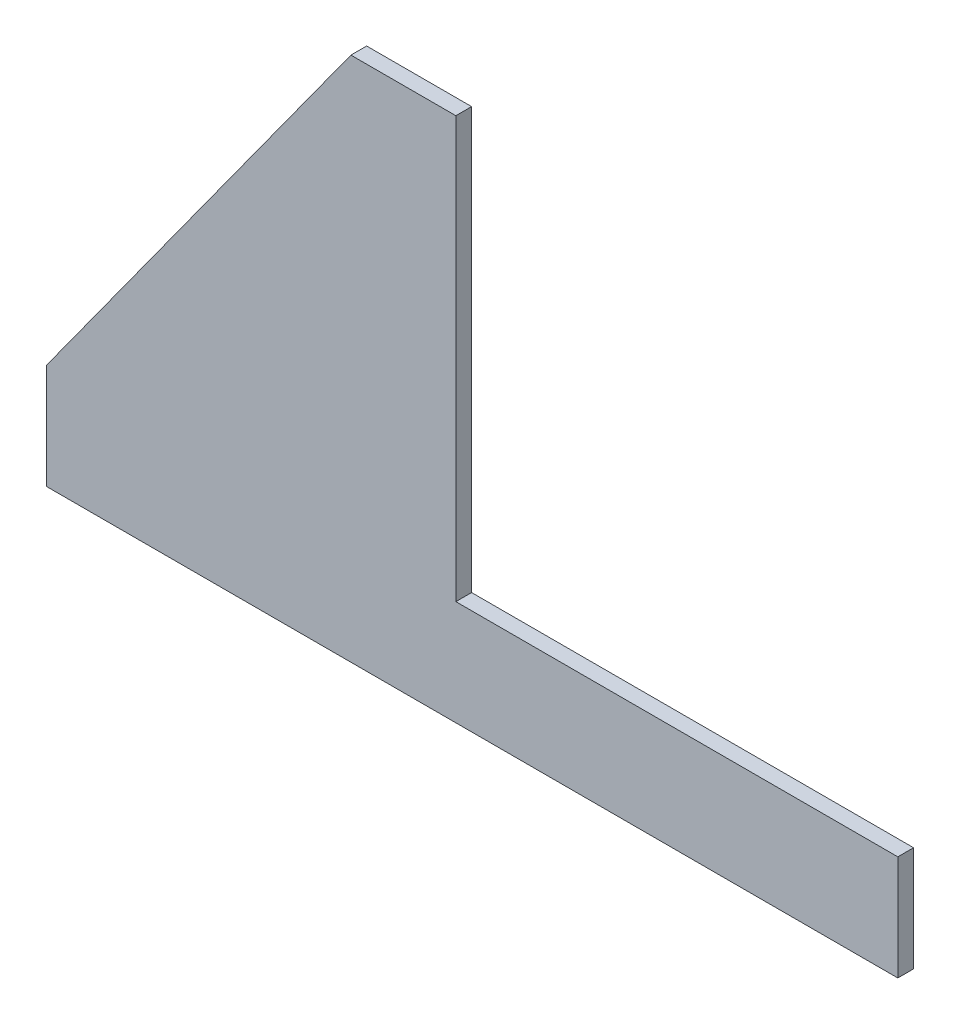
SolidWorks part; units mm, degrees
ref_plane "Alzado" through (0, 0, 0) normal (0, 0, 1) x (1, 0, 0)
ref_plane "Planta" through (0, 0, 0) normal (0, 1, 0) x (1, 0, 0)
ref_plane "Vista lateral" through (0, 0, 0) normal (1, 0, 0) x (0, 0, -1)
sketch "Croquis1" plane through (0, 0, 0) normal (0, 0, 1) x (1, 0, 0)
  line L0 (-15.5, 50) -> (405.6, 50)
  line L1 (-405.6, -50) -> (405.6, -50)
  line L2 (-405.6, -50) -> (-405.6, 50)
  line L3 (-405.6, 50) -> (-115.5, 451)
  line L4 (405.6, -50) -> (405.6, 50)
  line L5 (-405.6, -50) -> (405.6, 50) construction
  line L6 (-405.6, 50) -> (405.6, -50) construction
  line L7 (-115.5, 451) -> (-15.5, 451)
  line L8 (-15.5, 451) -> (-15.5, 50)
  line L9 (-405.6, 50) -> (-15.5, 50) construction
  point P0 (0, 0)
  dimension "D1" = 811.2
  dimension "D2" = 100
  dimension "D3" = 100
  dimension "D4" = 401
  dimension "D5" = 390.1
extrude "Saliente-Extruir1" add sketch "Croquis1" along normal blind 15
sketch "Croquis2" plane through (0, 0, 15) normal (0, 0, 1) x (1, 0, 0)
  line L0 (0, -50) -> (0, 50) construction
  line L3 (-405.6, 0) -> (405.6, 0) construction
  line L4 (-405.6, 50) -> (-405.6, -50) construction
  line L5 (405.6, -50) -> (405.6, 50) construction
  line L6 (-405.6, -50) -> (405.6, -50) construction
  line L7 (405.6, 50) -> (-15.5, 50) construction
sketch "Croquis3" plane through (0, 50, 0) normal (0, 1, 0) x (1, 0, 0)
  line L0 (0, -15) -> (0, 0) construction
